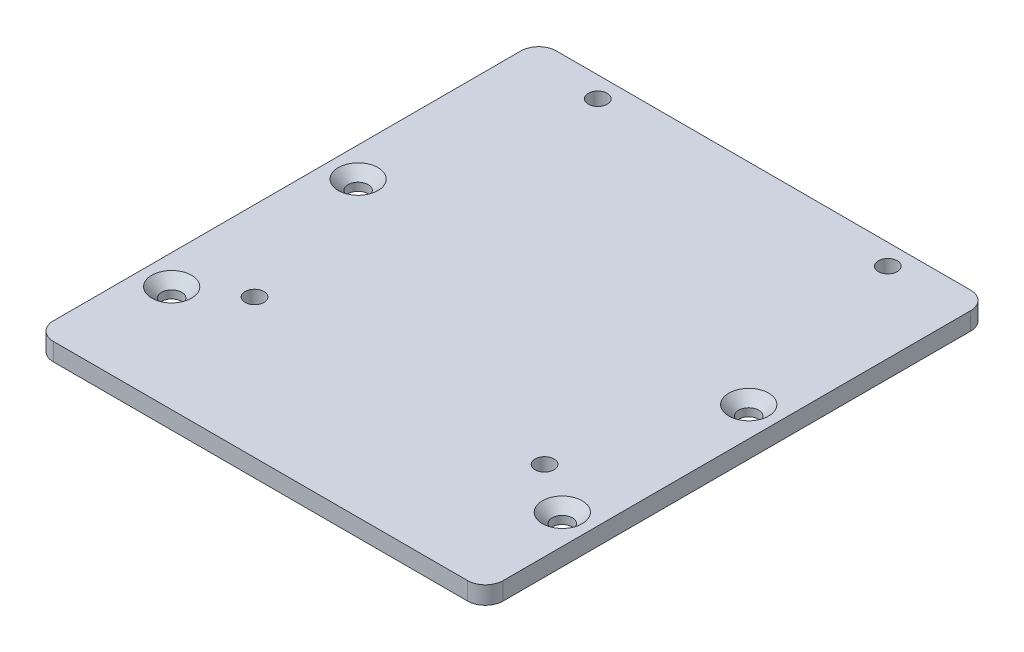
SolidWorks part; units mm, degrees
material "6061-T6 (SS)"
ref_plane "Front Plane" through (0, 0, 0) normal (0, 0, 1) x (1, 0, 0)
ref_plane "Top Plane" through (0, 0, 0) normal (0, 1, 0) x (1, 0, 0)
ref_plane "Right Plane" through (0, 0, 0) normal (1, 0, 0) x (0, 0, -1)
sketch "Sketch1" plane through (0, 0, 0) normal (0, 1, 0) x (1, 0, 0)
  line L0 (-33, 7) -> (-33, -24.5) construction
  line L1 (33, -24.5) -> (33, 7) construction
  line L2 (-33, 0) -> (33, 0) construction
  line L4 (38, -42.5) -> (-38, -42.5)
  line L5 (38, -42.5) -> (38, 42.5)
  line L6 (38, 42.5) -> (-38, 42.5)
  line L7 (-38, -42.5) -> (-38, 42.5)
  line L8 (38, -42.5) -> (-38, 42.5) construction
  line L9 (38, 42.5) -> (-38, -42.5) construction
  line L10 (24.5, -19) -> (-24.5, -19) construction
  line L11 (24.5, -19) -> (24.5, 39) construction
  line L12 (24.5, 39) -> (-24.5, 39) construction
  line L13 (-24.5, -19) -> (-24.5, 39) construction
  line L14 (24.5, -19) -> (-24.5, 39) construction
  line L15 (24.5, 39) -> (-24.5, -19) construction
  point P4 (0, 0)
  point P7 (0, 10)
  point P12 (0, 0)
  point P18 (0, 17.103)
  point P19 (0, 0)
  dimension "D1" = 31.5
  dimension "D2" = 7
  dimension "D3" = 85
  dimension "D4" = 76
  dimension "D5" = 49
  dimension "D6" = 58
  dimension "D7" = 3.5
  dimension "D8" = 5
extrude "Boss-Extrude1" add sketch "Sketch1" along normal blind 3
hole_wizard "M3 Clearance Hole1" positions "Sketch2" profile "Sketch3" hole size "M3" standard "ANSI Metric" end condition through all
sketch "Sketch2" plane through (0, 3, 0) normal (0, 1, 0) x (1, 0, 0)
  point P0 (-24.5, 39)
  point P3 (-24.5, -19)
  point P6 (24.5, -19)
  point P9 (24.5, 39)
sketch "Sketch3" plane through (-24.5, 3, -39) normal (1, 0, 0) x (0, 0, 1)
  line L0 (0, 0) -> (0, 3)
  line L1 (0, 3) -> (1.6, 3)
  line L2 (1.6, 3) -> (1.6, 0)
  line L5 (1.6, 0) -> (0, 0)
  line L11 (0, -6.35) -> (0, 107.95) construction
  dimension "Thru Hole Dia." = 3.2
  dimension "Thru Hole Depth" = 3
hole_wizard "CSK for M3 SFHCS1" positions "Sketch4" profile "Sketch5" countersink size "M3" standard "ANSI Metric" end condition through all
sketch "Sketch4" plane through (0, 3, 0) normal (0, 1, 0) x (1, 0, 0)
  point P0 (-33, -24.5)
  point P3 (-33, 7)
  point P6 (33, 7)
  point P9 (33, -24.5)
sketch "Sketch5" plane through (-33, 3, 24.5) normal (1, 0, 0) x (0, 0, 1)
  line L0 (0, 0) -> (0, 3)
  line L1 (0, 3) -> (1.7, 3)
  line L2 (1.7, 3) -> (1.7, 1.66)
  line L3 (1.7, 1.66) -> (3.36, 0)
  line L5 (3.36, 0) -> (0, 0)
  line L6 (-1.7, 1.66) -> (-3.36, 0) construction
  line L11 (0, -6.35) -> (0, 107.95) construction
  dimension "Thru Hole Dia." = 3.4
  dimension "Thru Hole Depth" = 3
  dimension "Near C'Sink Dia." = 6.72
  dimension "Near C'Sink Angle" = 90
fillet "Fillet1" radius 3 4 edges at (-38, 1.5, -42.5) (38, 1.5, -42.5) (38, 1.5, 42.5) (-38, 1.5, 42.5)
